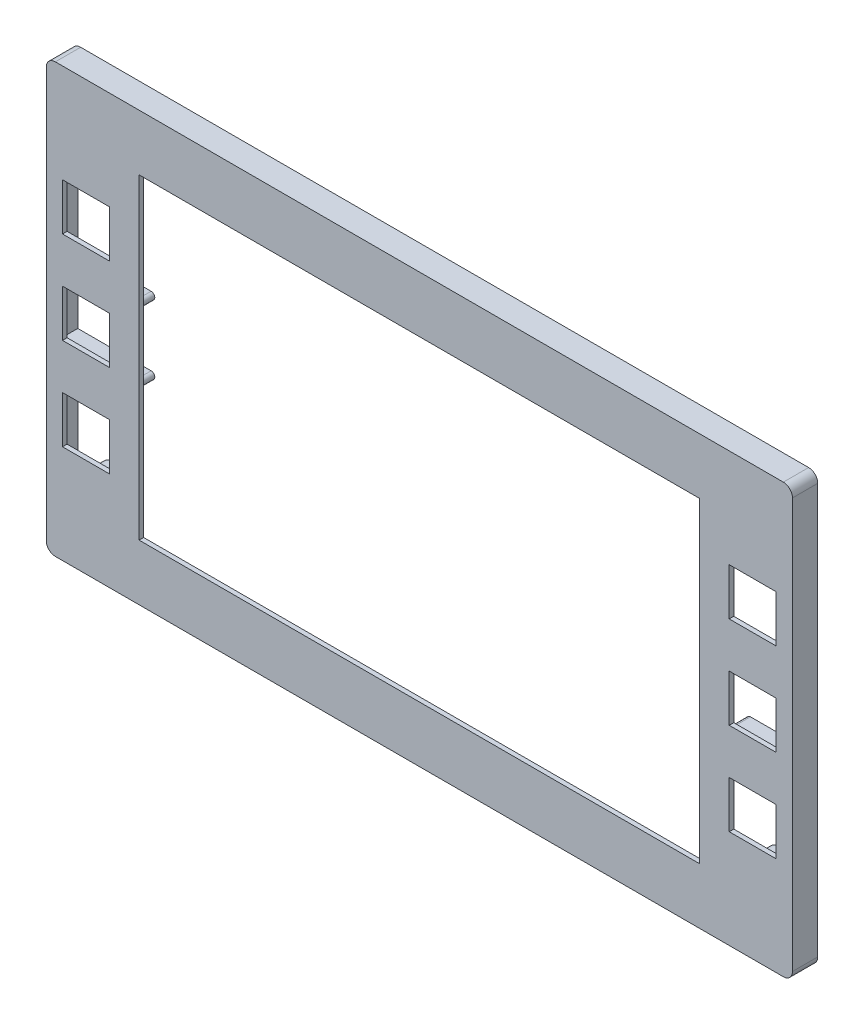
SolidWorks part; units mm, degrees
ref_plane "Front Plane" through (0, 0, 0) normal (0, 0, 1) x (1, 0, 0)
ref_plane "Top Plane" through (0, 0, 0) normal (0, 1, 0) x (1, 0, 0)
ref_plane "Right Plane" through (0, 0, 0) normal (1, 0, 0) x (0, 0, -1)
sketch "PCB" plane through (0, 0, 0) normal (0, 0, 1) x (1, 0, 0)
  line L0 (96.2635, 52.0314) -> (101.8921, 52.0314) construction
  line L1 (-101.8921, 57.66) -> (101.8921, 57.66) construction
  line L2 (-101.8921, 57.66) -> (-101.8921, -57.66) construction
  line L3 (-101.8921, -57.66) -> (101.8921, -57.66) construction
  line L4 (101.8921, 57.66) -> (101.8921, -57.66) construction
  line L5 (-101.8921, 57.66) -> (101.8921, -57.66) construction
  line L6 (-101.8921, -57.66) -> (101.8921, 57.66) construction
  line L7 (96.2635, 52.0314) -> (96.2635, 57.66) construction
  line L8 (-96.2635, 52.0314) -> (-101.8921, 52.0314) construction
  line L9 (-96.2635, -52.0314) -> (-96.2635, -57.66) construction
  line L10 (-92.8243, 0) -> (-92.8243, 25.66) construction
  line L11 (-98.8568, 31.6925) -> (-86.7918, 31.6925)
  line L12 (-98.8568, 31.6925) -> (-98.8568, 19.6275)
  line L13 (-98.8568, 19.6275) -> (-86.7918, 19.6275)
  line L14 (-86.7918, 31.6925) -> (-86.7918, 19.6275)
  line L15 (-98.8568, 31.6925) -> (-86.7918, 19.6275) construction
  line L16 (-98.8568, 19.6275) -> (-86.7918, 31.6925) construction
  line L17 (-98.8568, 6.0325) -> (-86.7918, 6.0325)
  line L18 (-98.8568, 6.0325) -> (-98.8568, -6.0325)
  line L19 (-98.8568, -6.0325) -> (-86.7918, -6.0325)
  line L20 (-86.7918, 6.0325) -> (-86.7918, -6.0325)
  line L21 (-98.8568, 6.0325) -> (-86.7918, -6.0325) construction
  line L22 (-98.8568, -6.0325) -> (-86.7918, 6.0325) construction
  line L23 (-98.8568, -19.6275) -> (-86.7918, -19.6275)
  line L24 (-98.8568, -19.6275) -> (-98.8568, -31.6925)
  line L25 (-98.8568, -31.6925) -> (-86.7918, -31.6925)
  line L26 (-86.7918, -19.6275) -> (-86.7918, -31.6925)
  line L27 (-98.8568, -19.6275) -> (-86.7918, -31.6925) construction
  line L28 (-98.8568, -31.6925) -> (-86.7918, -19.6275) construction
  line L29 (86.7918, 31.6925) -> (98.8568, 31.6925)
  line L30 (86.7918, 31.6925) -> (86.7918, 19.6275)
  line L31 (86.7918, 19.6275) -> (98.8568, 19.6275)
  line L32 (98.8568, 31.6925) -> (98.8568, 19.6275)
  line L33 (86.7918, 31.6925) -> (98.8568, 19.6275) construction
  line L34 (86.7918, 19.6275) -> (98.8568, 31.6925) construction
  line L35 (86.7918, 6.0325) -> (98.8568, 6.0325)
  line L36 (86.7918, 6.0325) -> (86.7918, -6.0325)
  line L37 (86.7918, -6.0325) -> (98.8568, -6.0325)
  line L38 (98.8568, 6.0325) -> (98.8568, -6.0325)
  line L39 (86.7918, 6.0325) -> (98.8568, -6.0325) construction
  line L40 (86.7918, -6.0325) -> (98.8568, 6.0325) construction
  line L41 (86.7918, -19.6275) -> (98.8568, -19.6275)
  line L42 (86.7918, -19.6275) -> (86.7918, -31.6925)
  line L43 (86.7918, -31.6925) -> (98.8568, -31.6925)
  line L44 (98.8568, -19.6275) -> (98.8568, -31.6925)
  line L45 (86.7918, -19.6275) -> (98.8568, -31.6925) construction
  line L46 (86.7918, -31.6925) -> (98.8568, -19.6275) construction
  line L47 (-92.8243, 0) -> (-92.8243, -25.66) construction
  line L48 (-92.8243, 25.66) -> (-101.8921, 25.66) construction
  line L49 (92.8243, 25.66) -> (101.8921, 25.66) construction
  circle A0 centre (-96.2635, 52.0314) radius 0.9995
  circle A1 centre (-96.2635, -52.0314) radius 0.9995
  circle A2 centre (96.2635, -52.0314) radius 0.9995
  circle A3 centre (96.2635, 52.0314) radius 0.9995
  point P0 (0, 0)
  point P14 (-92.8243, 25.66)
  point P23 (-92.8243, 0)
  point P28 (-92.8243, -25.66)
  point P33 (92.8243, 25.66)
  point P38 (92.8243, 0)
  point P43 (92.8243, -25.66)
  dimension "D4" = 1.999
  dimension "D1" = 203.7842
  dimension "D2" = 115.32
  dimension "D3" = 5.6286
  dimension "D5" = 32
  dimension "D6" = 32
  dimension "D7" = 9.0678
  dimension "D8" = 12.065
sketch "display_screen" plane through (0, 0, 0) normal (0, 0, 1) x (1, 0, 0)
  line L1 (-80.3275, 46.3296) -> (83.7565, 46.3296) construction
  line L2 (-80.3275, 46.3296) -> (-80.3275, -50.9016) construction
  line L3 (-80.3275, -50.9016) -> (83.7565, -50.9016) construction
  line L4 (83.7565, 46.3296) -> (83.7565, -50.9016) construction
  line L5 (-78.2955, 44.2976) -> (78.2955, 44.2976) construction
  line L6 (-78.2955, 44.2976) -> (-78.2955, -44.2976) construction
  line L7 (-78.2955, -44.2976) -> (78.2955, -44.2976) construction
  line L8 (78.2955, 44.2976) -> (78.2955, -44.2976) construction
  point P8 (0, 44.2976)
  point P10 (-78.2955, 0)
  dimension "D1" = 164.084
  dimension "D2" = 97.2312
  dimension "D3" = 6.604
  dimension "D4" = 2.032
  dimension "D5" = 2.032
  dimension "D6" = 5.461
ref_plane "foam_thickness" through (0, 0, 2.9972) normal (0, 0, 1) x (1, 0, 0)
ref_plane "face_of_screen" through (0, 0, 5.7658) normal (0, 0, 1) x (1, 0, 0)
sketch "Sketch1" plane through (0, 0, 0) normal (0, 0, 1) x (1, 0, 0)
  line L0 (83.7565, -54.2798) -> (83.7565, -57.89)
  line L1 (-103.8961, 59.64) -> (103.8961, 59.64)
  line L2 (-103.8961, 59.64) -> (-103.8961, -59.64)
  line L3 (-103.8961, -59.64) -> (103.8961, -59.64)
  line L4 (103.8961, 59.64) -> (103.8961, -59.64)
  line L5 (45.6565, 49.7078) -> (45.6565, 57.89)
  line L6 (-80.3275, 46.3296) -> (-80.3275, -50.9016) construction
  line L7 (45.6565, 57.89) -> (-42.2275, 57.89)
  line L8 (83.7565, 46.3296) -> (83.7565, -50.9016) construction
  line L9 (-102.1461, 57.89) -> (-102.1461, 59.64) construction
  line L10 (-102.1461, 57.89) -> (-103.8961, 57.89) construction
  line L11 (102.1461, -57.89) -> (103.8961, -57.89) construction
  line L12 (102.1461, -57.89) -> (102.1461, -59.64) construction
  line L13 (101.8921, 57.66) -> (101.8921, -57.66) construction
  line L14 (-80.3275, 49.7078) -> (-80.3275, 57.89)
  line L15 (-80.3275, 57.89) -> (-102.1461, 57.89)
  line L16 (-102.1461, 57.89) -> (-102.1461, 10.6085)
  line L17 (-101.8921, 57.66) -> (-101.8921, -57.66) construction
  line L18 (-102.1461, 10.6085) -> (-81.7265, 10.6085)
  line L19 (-42.2275, 57.89) -> (-42.2275, 49.7078)
  line L20 (77.4065, 49.7078) -> (77.4065, 57.89)
  line L21 (-81.7265, 8.5725) -> (-102.1461, 8.5725)
  line L22 (-102.1461, 8.5725) -> (-102.1461, -8.5725)
  line L23 (-102.1461, -8.5725) -> (-81.7265, -8.5725)
  line L24 (77.4065, 57.89) -> (52.0065, 57.89)
  line L25 (-81.7265, -10.6085) -> (-102.1461, -10.6085)
  line L26 (-102.1461, -10.6085) -> (-102.1461, -57.89)
  line L27 (52.0065, 49.7078) -> (52.0065, 57.89)
  line L28 (-80.3275, -50.9016) -> (83.7565, -50.9016) construction
  line L29 (52.0065, -54.2798) -> (52.0065, -57.89)
  line L30 (-48.5775, 49.7078) -> (-48.5775, 57.89)
  line L31 (-98.8568, 19.6275) -> (-86.7918, 19.6275) construction
  line L32 (-98.8568, 6.0325) -> (-86.7918, 6.0325) construction
  line L33 (-98.8568, -6.0325) -> (-86.7918, -6.0325) construction
  line L34 (-48.5775, 57.89) -> (-73.9775, 57.89)
  line L35 (-98.8568, -19.6275) -> (-86.7918, -19.6275) construction
  line L36 (-73.9775, 49.7078) -> (-73.9775, 57.89)
  line L37 (-101.8921, 57.66) -> (101.8921, 57.66) construction
  line L38 (83.7565, 49.7078) -> (83.7565, 57.89)
  line L39 (83.7565, 57.89) -> (102.1461, 57.89)
  line L40 (102.1461, 57.89) -> (102.1461, 10.6085)
  line L41 (-80.3275, 46.3296) -> (83.7565, 46.3296) construction
  line L42 (102.1461, 10.6085) -> (85.1555, 10.6085)
  line L43 (85.1555, 8.5725) -> (102.1461, 8.5725)
  line L44 (102.1461, 8.5725) -> (102.1461, -8.5725)
  line L45 (102.1461, -8.5725) -> (85.1555, -8.5725)
  line L46 (85.1555, -10.6085) -> (102.1461, -10.6085)
  line L47 (102.1461, -10.6085) -> (102.1461, -57.89)
  line L48 (102.1461, -57.89) -> (83.7565, -57.89)
  line L49 (83.7565, 57.89) -> (77.4065, 57.89) construction
  line L50 (52.0065, 57.89) -> (45.6565, 57.89) construction
  line L51 (-80.3275, 57.89) -> (-73.9775, 57.89) construction
  line L52 (-48.5775, 57.89) -> (-42.2275, 57.89) construction
  line L53 (-80.3275, -57.89) -> (-102.1461, -57.89)
  line L54 (-48.5775, -57.89) -> (-73.9775, -57.89)
  line L55 (45.6565, -57.89) -> (-42.2275, -57.89)
  line L56 (77.4065, -57.89) -> (52.0065, -57.89)
  line L57 (45.6565, -54.2798) -> (45.6565, -57.89)
  line L58 (77.4065, -54.2798) -> (77.4065, -57.89)
  line L59 (-42.2275, -54.2798) -> (-42.2275, -57.89)
  line L60 (-48.5775, -54.2798) -> (-48.5775, -57.89)
  line L61 (-73.9775, -54.2798) -> (-73.9775, -57.89)
  line L62 (-80.3275, -54.2798) -> (-80.3275, -57.89)
  line L63 (-101.8921, -57.66) -> (101.8921, -57.66) construction
  arc A0 (85.1555, -8.5725) -> (85.1555, -10.6085) centre (85.1555, -9.5905) ccw
  arc A1 (85.1555, 10.6085) -> (85.1555, 8.5725) centre (85.1555, 9.5905) ccw
  arc A2 (-81.7265, -10.6085) -> (-81.7265, -8.5725) centre (-81.7265, -9.5905) ccw
  arc A3 (-81.7265, 8.5725) -> (-81.7265, 10.6085) centre (-81.7265, 9.5905) ccw
  arc A4 (83.7565, 49.7078) -> (77.4065, 49.7078) centre (80.5815, 49.7078) cw
  arc A5 (52.0065, 49.7078) -> (45.6565, 49.7078) centre (48.8315, 49.7078) cw
  arc A6 (-80.3275, 49.7078) -> (-73.9775, 49.7078) centre (-77.1525, 49.7078) ccw
  arc A7 (-48.5775, 49.7078) -> (-42.2275, 49.7078) centre (-45.4025, 49.7078) ccw
  arc A8 (83.7565, -54.2798) -> (77.4065, -54.2798) centre (80.5815, -54.2798) ccw
  arc A9 (52.0065, -54.2798) -> (45.6565, -54.2798) centre (48.8315, -54.2798) ccw
  arc A10 (-80.3275, -54.2798) -> (-73.9775, -54.2798) centre (-77.1525, -54.2798) cw
  arc A11 (-48.5775, -54.2798) -> (-42.2275, -54.2798) centre (-45.4025, -54.2798) cw
  point P52 (84.1375, 9.5905)
  point P61 (-80.7085, 9.5905)
  point P72 (80.5815, 46.5328)
  point P80 (80.5815, -51.1048)
  point P86 (102.1461, -58.1652)
  point P92 (48.8315, -51.1048)
  point P93 (-77.1525, -51.1048)
  point P94 (-45.4025, -51.1048)
  dimension "D2" = 9.019
  dimension "D3" = 2.54
  dimension "D4" = 2.54
  dimension "D5" = 9.019
  dimension "D6" = 0.23
  dimension "D7" = 0.254
  dimension "D8" = 0.23
  dimension "D9" = 0.254
  dimension "D10" = 0.381
  dimension "D11" = 0.381
  dimension "D12" = 0.2032
  dimension "D13" = 6.35
  dimension "D14" = 25.4
  dimension "D15" = 0.2032
  dimension "D16" = 1.75
extrude "Boss-Extrude1" add sketch "Sketch1" along normal up to surface (5.7658 mm away) up to plane "face_of_screen"
sketch "Sketch2" plane through (0, 0, 5.7658) normal (0, 0, 1) x (1, 0, 0)
  line L0 (-78.0415, 44.0436) -> (-78.0415, 44.2976) construction
  line L1 (-103.8961, 59.64) -> (103.8961, 59.64)
  line L2 (-103.8961, 59.64) -> (-103.8961, -59.64)
  line L3 (-103.8961, -59.64) -> (103.8961, -59.64)
  line L4 (103.8961, 59.64) -> (103.8961, -59.64)
  line L5 (86.7918, 19.6275) -> (98.8568, 31.6925) construction
  line L6 (99.3648, 32.2005) -> (86.2838, 32.2005)
  line L7 (99.3648, 32.2005) -> (99.3648, 19.1195)
  line L8 (99.3648, 19.1195) -> (86.2838, 19.1195)
  line L9 (86.2838, 32.2005) -> (86.2838, 19.1195)
  line L10 (99.3648, 32.2005) -> (86.2838, 19.1195) construction
  line L11 (99.3648, 19.1195) -> (86.2838, 32.2005) construction
  line L12 (86.7918, 31.6925) -> (98.8568, 31.6925) construction
  line L13 (99.3648, 6.5405) -> (86.2838, 6.5405)
  line L14 (99.3648, 6.5405) -> (99.3648, -6.5405)
  line L15 (99.3648, -6.5405) -> (86.2838, -6.5405)
  line L16 (86.2838, 6.5405) -> (86.2838, -6.5405)
  line L17 (99.3648, 6.5405) -> (86.2838, -6.5405) construction
  line L18 (99.3648, -6.5405) -> (86.2838, 6.5405) construction
  line L19 (99.3648, -19.1195) -> (86.2838, -19.1195)
  line L20 (99.3648, -19.1195) -> (99.3648, -32.2005)
  line L21 (99.3648, -32.2005) -> (86.2838, -32.2005)
  line L22 (86.2838, -19.1195) -> (86.2838, -32.2005)
  line L23 (99.3648, -19.1195) -> (86.2838, -32.2005) construction
  line L24 (99.3648, -32.2005) -> (86.2838, -19.1195) construction
  line L25 (-86.2838, -19.1195) -> (-99.3648, -19.1195)
  line L26 (-86.2838, -19.1195) -> (-86.2838, -32.2005)
  line L27 (-86.2838, -32.2005) -> (-99.3648, -32.2005)
  line L28 (-99.3648, -19.1195) -> (-99.3648, -32.2005)
  line L29 (-78.0415, 44.0436) -> (78.0415, 44.0436)
  line L30 (-78.0415, 44.0436) -> (-78.0415, -44.0436)
  line L31 (-78.0415, -44.0436) -> (78.0415, -44.0436)
  line L32 (78.0415, 44.0436) -> (78.0415, -44.0436)
  line L33 (-78.2955, 44.2976) -> (78.2955, 44.2976) construction
  line L34 (-78.0415, 44.0436) -> (-78.2955, 44.0436) construction
  line L35 (-78.2955, 44.2976) -> (-78.2955, -44.2976) construction
  line L36 (78.0415, -44.0436) -> (78.2955, -44.0436) construction
  line L37 (78.2955, 44.2976) -> (78.2955, -44.2976) construction
  line L38 (78.0415, -44.0436) -> (78.0415, -44.2976) construction
  line L39 (-78.2955, -44.2976) -> (78.2955, -44.2976) construction
  line L40 (-86.2838, -19.1195) -> (-99.3648, -32.2005) construction
  line L41 (-86.2838, -32.2005) -> (-99.3648, -19.1195) construction
  line L42 (-99.3648, 6.5405) -> (-86.2838, 6.5405)
  line L43 (-99.3648, 6.5405) -> (-99.3648, -6.5405)
  line L44 (-99.3648, -6.5405) -> (-86.2838, -6.5405)
  line L45 (-86.2838, 6.5405) -> (-86.2838, -6.5405)
  line L46 (-99.3648, 6.5405) -> (-86.2838, -6.5405) construction
  line L47 (-99.3648, -6.5405) -> (-86.2838, 6.5405) construction
  line L48 (-99.3648, 32.2005) -> (-86.2838, 32.2005)
  line L49 (-99.3648, 32.2005) -> (-99.3648, 19.1195)
  line L50 (-99.3648, 19.1195) -> (-86.2838, 19.1195)
  line L51 (-86.2838, 32.2005) -> (-86.2838, 19.1195)
  line L52 (-99.3648, 32.2005) -> (-86.2838, 19.1195) construction
  line L53 (-99.3648, 19.1195) -> (-86.2838, 32.2005) construction
  point P6 (92.8243, 25.66)
  point P15 (92.8243, 0)
  point P24 (92.8243, -25.66)
  point P31 (-92.8243, -25.66)
  point P38 (-92.8243, 0)
  point P65 (-92.8243, 25.66)
  dimension "D1" = 0.254
  dimension "D2" = 0.508
extrude "Boss-Extrude2" add sketch "Sketch2" along normal blind 1.27
fillet "Fillet1" radius 2.54 4 edges at (-103.8961, -59.64, 3.5179) (103.8961, -59.64, 3.5179) (-103.8961, 59.64, 3.5179) (103.8961, 59.64, 3.5179)
sketch "Sketch3" plane through (0, 0, 5.7658) normal (0, 0, -1) x (-1, 0, 0)
  line L0 (-92.825, 38.5525) -> (-92.825, 57.89) construction
  line L1 (-92.825, 38.5525) -> (92.825, 38.5525) construction
  line L2 (-92.825, 38.5525) -> (-92.825, -38.5525) construction
  line L3 (-92.825, -38.5525) -> (92.825, -38.5525) construction
  line L4 (92.825, 38.5525) -> (92.825, -38.5525) construction
  line L5 (-102.1461, 57.89) -> (-83.7565, 57.89) construction
  line L6 (-92.825, 38.5525) -> (-102.1461, 38.5525) construction
  line L7 (-102.1461, 10.6085) -> (-102.1461, 57.89) construction
  line L8 (92.825, -38.5525) -> (102.1461, -38.5525) construction
  line L9 (102.1461, -10.6085) -> (102.1461, -57.89) construction
  line L10 (92.825, -38.5525) -> (92.825, -57.89) construction
  line L11 (102.1461, -57.89) -> (80.3275, -57.89) construction
  circle A0 centre (-92.825, 38.5525) radius 1.125
  circle A1 centre (-92.825, 38.5525) radius 2.625
  circle A2 centre (92.825, 38.5525) radius 1.125
  circle A3 centre (92.825, 38.5525) radius 2.625
  circle A4 centre (-92.825, -38.5525) radius 1.125
  circle A5 centre (-92.825, -38.5525) radius 2.625
  circle A6 centre (92.825, -38.5525) radius 1.125
  circle A7 centre (92.825, -38.5525) radius 2.625
  circle A8 centre (0, 53.4525) radius 1.125
  circle A9 centre (0, 53.4525) radius 2.625
  circle A10 centre (0, -53.4525) radius 1.125
  circle A11 centre (0, -53.4525) radius 2.625
  point P30 (0, 0)
  dimension "D1" = 2.25
  dimension "D2" = 1.5
  dimension "D3" = 185.65
  dimension "D4" = 77.105
  dimension "D5" = 14.9
  dimension "D6" = 14.9
extrude "Boss-Extrude3" add sketch "Sketch3" along normal up to surface (5.7658 mm away) up to face at (0, 0, 0)
fillet "Fillet2" radius 2 6 edges at (95.45, -38.5525, 5.7658) (-90.2, -38.5525, 5.7658) (-90.2, 38.5525, 5.7658) (95.45, 38.5525, 5.7658) (2.625, -53.4525, 5.7658) (2.625, 53.4525, 5.7658)
sketch "Sketch4" plane through (0, 0, 0) normal (0, 0, -1) x (-1, 0, 0)
  line L0 (0, -50.8275) -> (0, -51.1275) construction
  line L1 (-5, -51.1275) -> (5, -51.1275)
  line L2 (-5, -51.1275) -> (-5, -47.1275)
  line L3 (-5, -47.1275) -> (5, -47.1275)
  line L4 (5, -51.1275) -> (5, -47.1275)
  circle A0 centre (0, -53.4525) radius 2.625 construction
  circle A1 centre (0, -53.4525) radius 2.625 construction
  point P4 (0, -47.1275)
  dimension "D3" = 0.3
  dimension "D1" = 10
  dimension "D2" = 4
extrude "Cut-Extrude2" cut sketch "Sketch4" against normal up to surface (5.7658 mm away) up to face at (97.45, -38.5525, 5.7658)
